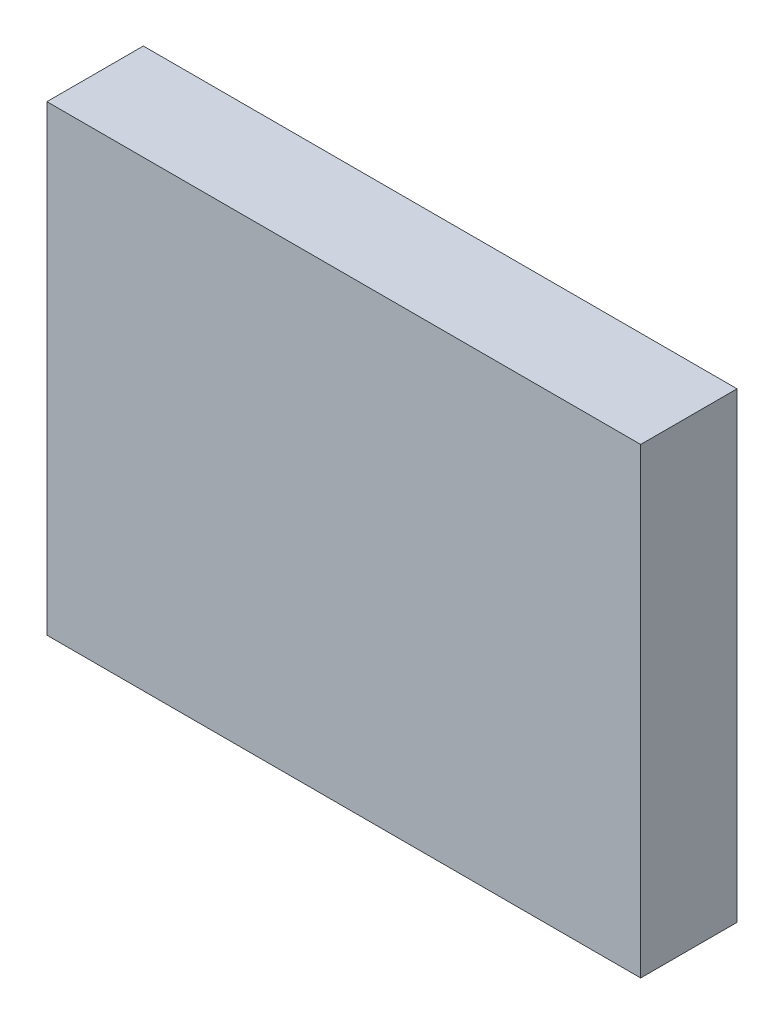
SolidWorks part; units mm, degrees
ref_plane "Front Plane" through (0, 0, 0) normal (0, 0, 1) x (1, 0, 0)
ref_plane "Top Plane" through (0, 0, 0) normal (0, 1, 0) x (1, 0, 0)
ref_plane "Right Plane" through (0, 0, 0) normal (1, 0, 0) x (0, 0, -1)
sketch "Sketch1" plane through (0, 0, 0) normal (0, 0, 1) x (1, 0, 0)
  line L1 (0, 0) -> (61.6032, 0)
  line L2 (0, 0) -> (0, 47.9423)
  line L3 (0, 47.9423) -> (61.6032, 47.9423)
  line L4 (61.6032, 0) -> (61.6032, 47.9423)
extrude "Boss-Extrude1" add sketch "Sketch1" along normal blind 10
